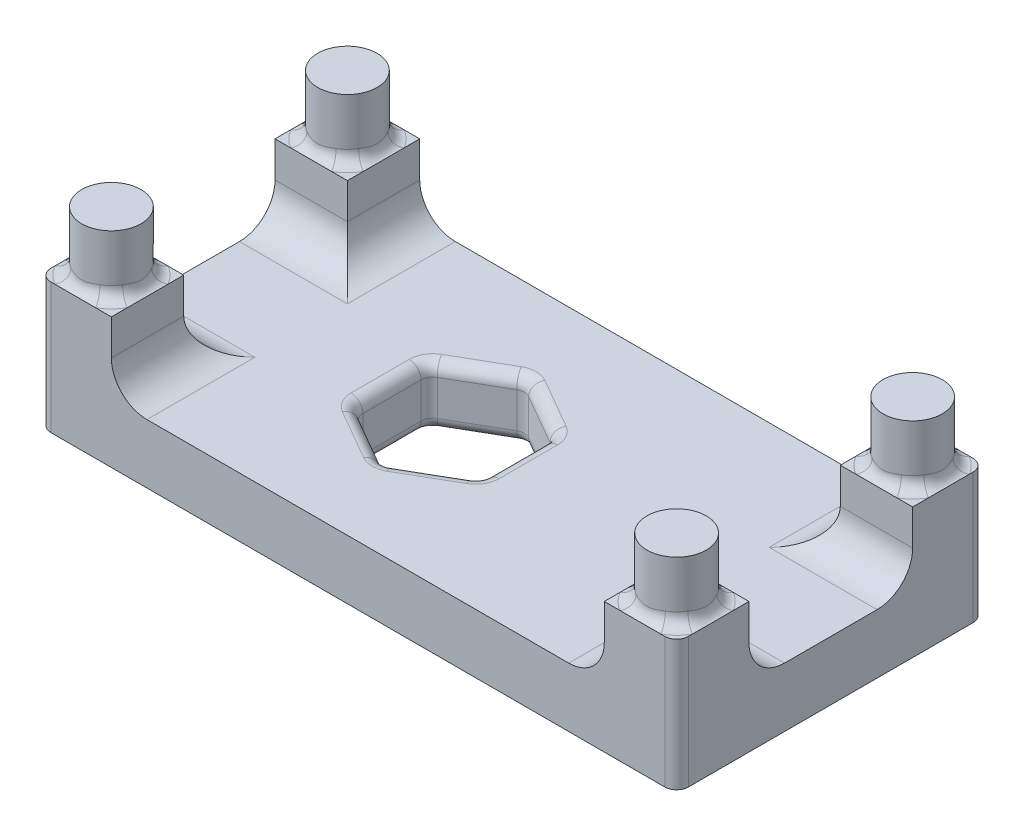
SolidWorks part; units mm, degrees
note: The reader was unsure of these and kept them because the rebuilt part matched: shared geometry of "Sketch2<3>", "Sketch2<4>".
ref_plane "Front Plane" through (0, 0, 0) normal (0, 0, 1) x (1, 0, 0)
ref_plane "Top Plane" through (0, 0, 0) normal (0, 1, 0) x (1, 0, 0)
ref_plane "Right Plane" through (0, 0, 0) normal (1, 0, 0) x (0, 0, -1)
sketch "Sketch2" plane through (0, 0, 0) normal (0, 1, 0) x (1, 0, 0)
  line L4 (-26.88, -13) -> (26.88, -13)
  line L15 (26.88, -13) -> (26.88, 13)
  line L16 (26.88, 13) -> (-26.88, 13)
  line L17 (-26.88, 13) -> (-26.88, -13)
  line L18 (0, 0) -> (26.88, 0)
  line L19 (0, 0) -> (-26.88, 0)
  line L21 (-4.87, -6.0622) -> (0.38, -3.0311)
  line L22 (0.38, -3.0311) -> (0.38, 3.0311)
  line L23 (0.38, 3.0311) -> (-4.87, 6.0622)
  line L24 (-4.87, 6.0622) -> (-10.12, 3.0311)
  line L25 (-10.12, 3.0311) -> (-10.12, -3.0311)
  line L26 (-10.12, -3.0311) -> (-4.87, -6.0622)
  line L27 (-26.88, 6.9) -> (-20.78, 6.9)
  line L28 (-26.88, 6.9) -> (-26.88, 13)
  line L29 (-26.88, 13) -> (-20.78, 13)
  line L30 (-20.78, 6.9) -> (-20.78, 13)
  line L35 (20.78, 6.9) -> (26.88, 6.9)
  line L36 (20.78, 6.9) -> (20.78, 13)
  line L37 (20.78, 13) -> (26.88, 13)
  line L38 (26.88, 6.9) -> (26.88, 13)
  line L39 (20.78, -6.9) -> (26.88, -6.9)
  line L40 (20.78, -6.9) -> (20.78, -13)
  line L41 (20.78, -13) -> (26.88, -13)
  line L42 (26.88, -6.9) -> (26.88, -13)
  line L43 (-20.78, -6.9) -> (-26.88, -6.9)
  line L44 (-20.78, -6.9) -> (-20.78, -13)
  line L45 (-20.78, -13) -> (-26.88, -13)
  line L46 (-26.88, -6.9) -> (-26.88, -13)
  circle A0 centre (-4.87, 0) radius 5.25 construction
  circle A4 centre (23.83, -9.95) radius 3.05
  circle A5 centre (23.83, -9.95) radius 2.5
  circle A6 centre (23.83, 9.95) radius 3.05
  circle A7 centre (23.83, 9.95) radius 2.5
  circle A8 centre (-23.83, 9.95) radius 3.05
  circle A9 centre (-23.83, 9.95) radius 2.5
  circle A10 centre (-23.83, -9.95) radius 3.05
  circle A11 centre (-23.83, -9.95) radius 2.5
  dimension "D1" = 10.5
  dimension "D3" = 6.1
  dimension "D4" = 5
  dimension "D5" = 9.95
  dimension "D2" = 47.66
  dimension "D6" = 18.96
extrude "Boss-Extrude1" add sketch "Sketch2" along normal blind 5
extrude "Boss-Extrude2" add sketch "Sketch2<3>" along normal blind 11 contours L46 L43 L44 L45 | L28 L27 L30 L29 | L37 L36 L35 L38 | L42 L39 L40 L41
sketch "Sketch2<3>" plane through (0, 0, 0) normal (0, 1, 0) x (1, 0, 0) same geometry as "Sketch2"
extrude "Boss-Extrude3" add sketch "Sketch2<4>" along normal blind 16 contours A11 | A9 | A7 | A5
sketch "Sketch2<4>" plane through (0, 0, 0) normal (0, 1, 0) x (1, 0, 0) same geometry as "Sketch2"
fillet "Fillet1" radius 1 4 edges at (23.83, 11, 7.45) (23.83, 11, -12.45) (-23.83, 11, -7.45) (-23.83, 11, 12.45)
fillet "Fillet2" radius 1 10 edges at (0.38, 2.5, -3.0311) (0.38, 2.5, 3.0311) (-26.88, 5.5, -13) (26.88, 5.5, -13) (26.88, 5.5, 13) (-26.88, 5.5, 13) (-4.87, 2.5, -6.0622) (-10.12, 2.5, -3.0311) (-10.12, 2.5, 3.0311) (-4.87, 2.5, 6.0622)
fillet "Fillet3" radius 1 24 edges at (-2.245, 0, -4.5466) (-2.245, 5, -4.5466) (0.246, 5, -2.9537) (0.246, 0, -2.9537) (0.38, 5, 0) (0.38, 0, 0) (0.246, 5, 2.9537) (0.246, 0, 2.9537) (-2.245, 5, 4.5466) (-2.245, 0, 4.5466) (-4.87, 5, 5.9075) (-4.87, 0, 5.9075) (-7.495, 0, 4.5466) (-7.495, 5, 4.5466) (-9.986, 5, 2.9537) (-9.986, 0, 2.9537) (-10.12, 0, 0) (-10.12, 5, 0) (-9.986, 5, -2.9537) (-9.986, 0, -2.9537) (-7.495, 0, -4.5466) (-7.495, 5, -4.5466) (-4.87, 5, -5.9075) (-4.87, 0, -5.9075)
fillet "Fillet4" radius 3 8 edges at (-23.83, 5, 6.9) (-20.78, 5, 9.95) (20.78, 5, 9.95) (23.83, 5, 6.9) (23.83, 5, -6.9) (20.78, 5, -9.95) (-20.78, 5, -9.95) (-23.83, 5, -6.9)
